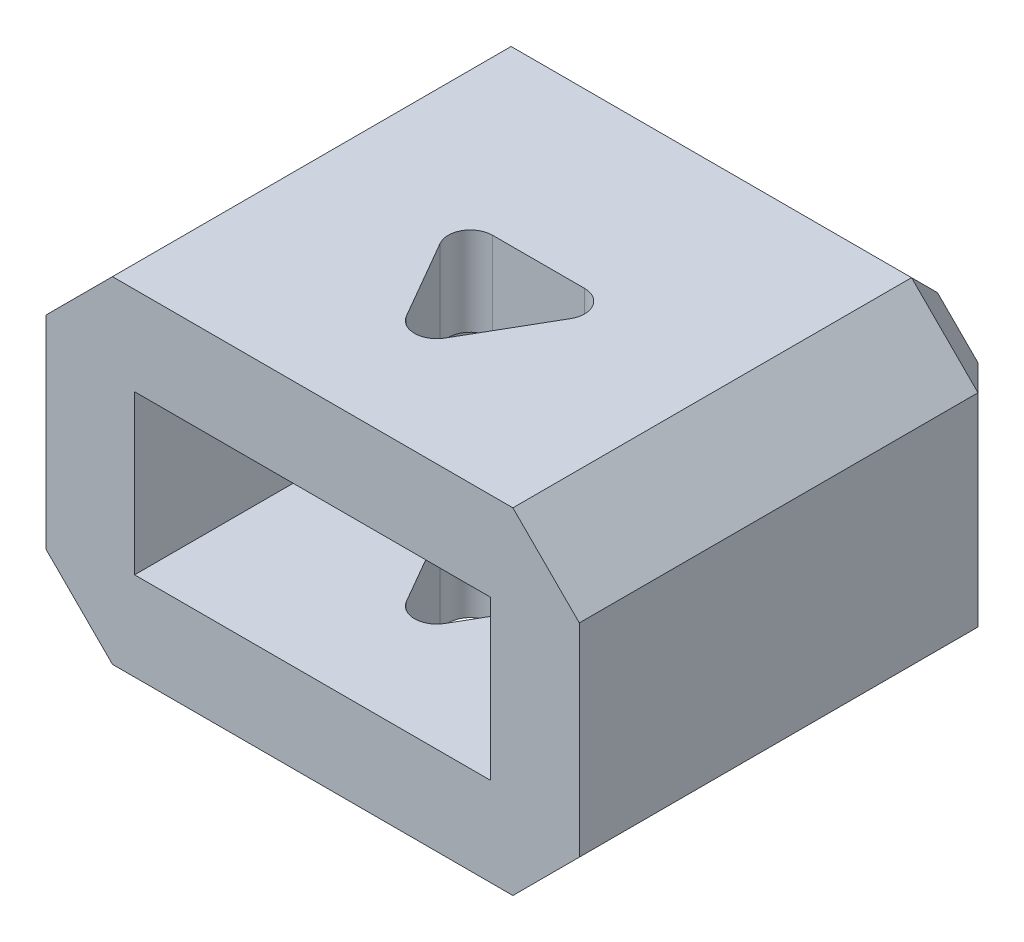
SolidWorks part; units mm, degrees
ref_plane "Front Plane" through (0, 0, 0) normal (0, 0, 1) x (1, 0, 0)
ref_plane "Top Plane" through (0, 0, 0) normal (0, 1, 0) x (1, 0, 0)
ref_plane "Right Plane" through (0, 0, 0) normal (1, 0, 0) x (0, 0, -1)
sketch "Sketch1" plane through (0, 0, 0) normal (0, 0, 1) x (1, 0, 0)
  line L1 (4.02, -1.79) -> (-4.02, -1.79)
  line L2 (4.02, -1.79) -> (4.02, 1.79)
  line L3 (4.02, 1.79) -> (-4.02, 1.79)
  line L4 (-4.02, -1.79) -> (-4.02, 1.79)
  line L5 (0, 1.79) -> (0, -1.79) construction
  line L6 (4.02, 0) -> (-4.02, 0) construction
  line L7 (-6.02, 3.79) -> (6.02, 3.79)
  line L8 (-6.02, 3.79) -> (-6.02, -3.79)
  line L9 (-6.02, -3.79) -> (6.02, -3.79)
  line L10 (6.02, 3.79) -> (6.02, -3.79)
  line L11 (0, -3.79) -> (0, 3.79) construction
  line L12 (-6.02, 0) -> (6.02, 0) construction
  point P0 (0, 0)
  point P4 (0, 0)
  dimension "D1" = 3.58
  dimension "D2" = 8.04
  dimension "D3" = 2
  dimension "D4" = 2
extrude "Boss-Extrude1" add sketch "Sketch1" along normal blind 8
extrude "Boss-Extrude2" add sketch "Sketch1<2>" against normal blind 2 contours L4 L1 L2 L3 | L10 L7 L8 L9 L1 L4 L3 L2 region at (0, 0, 0) region at (0, 3.6477, 0)
sketch "Sketch1<2>" plane through (0, 0, 0) normal (0, 0, 1) x (1, 0, 0) same geometry as "Sketch1"
chamfer "Chamfer1" distance 1.5 angle 45 4 edges at (-6.02, -3.79, 3) (-6.02, 3.79, 3) (6.02, 3.79, 3) (6.02, -3.79, 3)
sketch "Sketch2" plane through (0, -3.79, 0) normal (0, -1, 0) x (1, 0, 0)
  line L0 (-4.52, -2) -> (4.52, -2) construction
  line L1 (-1.9053, 2.9) -> (1.9053, 2.9)
  line L2 (1.9053, 2.9) -> (0, 6.2)
  line L3 (0, 6.2) -> (-1.9053, 2.9)
  circle A0 centre (0, 4) radius 1.1 construction
  dimension "D2" = 2.2
  dimension "D1" = 4
extrude "Cut-Extrude1" cut sketch "Sketch2" against normal through all both and the other way through all
fillet "Fillet1" radius 0.5 6 edges at (-1.9053, 2.79, 2.9) (0, 2.79, 6.2) (1.9053, 2.79, 2.9) (1.9053, -2.79, 2.9) (0, -2.79, 6.2) (-1.9053, -2.79, 2.9)
chamfer "Chamfer2" distance 1 angle 45 8 edges at (5.27, -3.04, -2) (6.02, 0, -2) (5.27, 3.04, -2) (0, 3.79, -2) (-5.27, 3.04, -2) (-6.02, 0, -2) (-5.27, -3.04, -2) (0, -3.79, -2)
equation "\"LF\" = 0.04mm"
equation "\"TF\" = 0.02mm"
equation "\"AngLF\"= 0.5"
equation "\"AngTF\"= 0.3"
equation "\"D2@Sketch1\"=8+2*\"TF\""
equation "\"D1@Sketch1\"=3.5+2*\"LF\""
